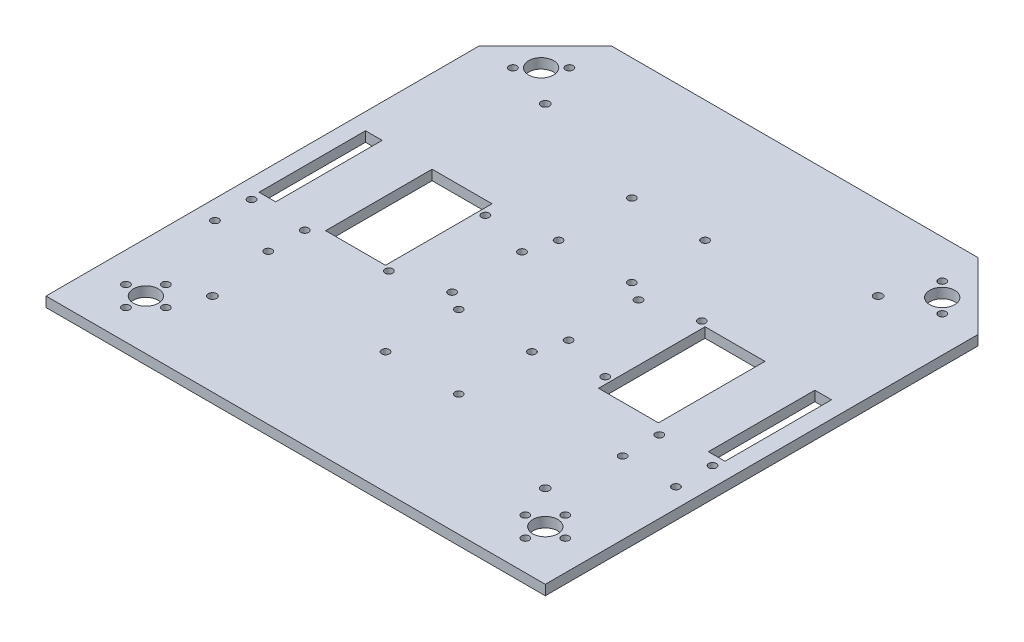
SolidWorks part; units mm, degrees
ref_plane "Plan de face" through (0, 0, 0) normal (0, 0, 1) x (1, 0, 0)
ref_plane "Plan de dessus" through (0, 0, 0) normal (0, 1, 0) x (1, 0, 0)
ref_plane "Plan de droite" through (0, 0, 0) normal (1, 0, 0) x (0, 0, -1)
sketch "Esquisse1" plane through (0, 0, 0) normal (0, 1, 0) x (1, 0, 0)
  line L0 (-150, 0) -> (-150, 260)
  line L2 (150, 0) -> (150, 260)
  line L3 (-150, 260) -> (-110, 260) construction
  line L4 (-110, 260) -> (-110, 300) construction
  line L5 (150, 260) -> (110, 260) construction
  line L6 (110, 260) -> (110, 300) construction
  line L8 (-150, 260) -> (-110, 300)
  line L9 (-110, 300) -> (110, 300)
  line L10 (0, 0) -> (0, 300) construction
  line L11 (110, 300) -> (150, 260)
  line L12 (-150, 0) -> (-120, 0) construction
  line L13 (-120, 18) -> (-120, 0) construction
  line L14 (150, 0) -> (120, 0) construction
  line L15 (120, 18) -> (120, 0) construction
  line L17 (-150, 260) -> (-120, 260) construction
  line L18 (-120, 260) -> (-120, 267.5) construction
  line L19 (150, 260) -> (120, 260) construction
  line L20 (120, 260) -> (120, 268.5) construction
  line L21 (-120, 267.5) -> (-111.5147, 275.9853) construction
  line L22 (-120, 267.5) -> (-128.4853, 259.0147) construction
  line L23 (120, 268.5) -> (128.4853, 260.0147) construction
  line L24 (120, 268.5) -> (111.5147, 276.9853) construction
  line L25 (-150, 0) -> (150, 0) construction
  line L26 (120, 30) -> (120, 18) construction
  line L27 (120, 30) -> (120, 42) construction
  line L28 (-150, 0) -> (150, 0)
  line L29 (-120, 18) -> (-120, 30) construction
  line L30 (-120, 30) -> (-120, 42) construction
  line L32 (150, 150) -> (-150, 150) construction
  line L33 (-120, 30) -> (-108, 30) construction
  line L34 (-120, 30) -> (-132, 30) construction
  line L35 (120, 30) -> (132, 30) construction
  line L36 (120, 30) -> (108, 30) construction
  circle A2 centre (-120, 30) radius 7.5
  circle A4 centre (-120, 267.5) radius 7.5
  circle A5 centre (120, 268.5) radius 7.5
  circle A6 centre (-111.5147, 275.9853) radius 2.3
  circle A7 centre (-128.4853, 259.0147) radius 2.3
  circle A8 centre (111.5147, 276.9853) radius 2.3
  circle A9 centre (128.4853, 260.0147) radius 2.3
  circle A10 centre (120, 30) radius 7.5
  circle A11 centre (120, 42) radius 2.3
  circle A13 centre (-120, 42) radius 2.3
  circle A14 centre (-120, 18) radius 2.3
  circle A16 centre (-132, 30) radius 2.3
  circle A17 centre (-108, 30) radius 2.3
  circle A18 centre (108, 30) radius 2.3
  circle A19 centre (132, 30) radius 2.3
  circle A20 centre (120, 18) radius 2.3
extrude "Boss.-Extru.1" add sketch "Esquisse1" along normal blind 6
sketch "Esquisse7" plane through (0, 6, 0) normal (0, 1, 0) x (1, 0, 0)
  line L0 (0, 150) -> (-130, 150) construction
  line L1 (0, 0) -> (0, 300) construction
  line L2 (150, 150) -> (-150, 150) construction
  line L3 (-130, 150) -> (-130, 182)
  line L4 (-130, 182) -> (-140, 182)
  line L5 (-140, 182) -> (-140, 118)
  line L6 (-140, 118) -> (-130, 118)
  line L7 (-130, 118) -> (-130, 150)
extrude "Enlèv. mat.-Extru.9" cut sketch "Esquisse7" against normal blind 10.5
sketch "Esquisse6" plane through (0, 6, 0) normal (0, 1, 0) x (1, 0, 0)
  line L0 (-142.5, 116) -> (-134.5, 116) construction
  line L2 (-142.5, 116) -> (-142.5, 150) construction
  line L3 (-142.5, 116) -> (-142.5, 108) construction
  line L11 (-142.5, 108) -> (-134.5, 108) construction
  line L12 (-134.5, 108) -> (-134.5, 116) construction
  line L14 (-142.5, 150) -> (-150, 150) construction
  line L15 (-142.5, 116) -> (-102.5, 116) construction
  line L16 (-102.5, 116) -> (-102.5, 108) construction
  line L17 (-102.5, 108) -> (-110.5, 108) construction
  line L18 (-110.5, 108) -> (-110.5, 116) construction
  line L19 (-110.5, 116) -> (-134.5, 116) construction
  line L20 (-134.5, 116) -> (-134.5, 86) construction
  line L21 (-134.5, 86) -> (-142.5, 86) construction
  line L22 (-142.5, 86) -> (-142.5, 94) construction
  line L23 (-142.5, 94) -> (-134.5, 94) construction
  line L24 (-134.5, 94) -> (-134.5, 86) construction
  line L25 (-134.5, 86) -> (-110.5, 86) construction
  line L26 (-110.5, 86) -> (-110.5, 94) construction
  line L27 (-110.5, 94) -> (-102.5, 94) construction
  line L28 (-102.5, 94) -> (-102.5, 86) construction
  line L29 (-102.5, 86) -> (-110.5, 86) construction
  line L30 (-102.5, 94) -> (-110.5, 86) construction
  line L31 (-110.5, 94) -> (-102.5, 86) construction
  line L32 (-142.5, 94) -> (-134.5, 86) construction
  line L33 (-142.5, 86) -> (-134.5, 94) construction
  line L34 (-142.5, 116) -> (-134.5, 108) construction
  line L35 (-142.5, 108) -> (-134.5, 116) construction
  line L71 (-110.5, 116) -> (-102.5, 108) construction
  line L72 (-110.5, 108) -> (-102.5, 116) construction
  line L73 (-110.5, 116) -> (-110.5, 86) construction
  circle A20 centre (-138.5, 90) radius 2.3
  circle A21 centre (-138.5, 112) radius 2.3
  circle A22 centre (-106.5, 112) radius 2.3
  circle A23 centre (-106.5, 90) radius 2.3
  dimension "D1" = 7.5
  dimension "D2" = 34
sketch "Esquisse4" plane through (0, 6, 0) normal (0, 1, 0) x (1, 0, 0)
  line L0 (-150, 150) -> (-100, 150) construction
  line L8 (150, 150) -> (-150, 150) construction
  line L14 (-100, 150) -> (-100, 182)
  line L15 (-100, 250) -> (-100, 50) construction
  line L16 (-100, 150) -> (-100, 118)
  line L17 (-100, 118) -> (-64, 118)
  line L18 (-64, 118) -> (-64, 182)
  line L19 (-64, 182) -> (-100, 182)
sketch "Esquisse9" plane through (0, 6, 0) normal (0, 1, 0) x (1, 0, 0)
  line L0 (-150, 0) -> (150, 0) construction
  line L1 (150, 0) -> (150, 300) construction
  line L2 (150, 300) -> (-150, 300) construction
  line L3 (-150, 300) -> (-150, 0) construction
  line L5 (-150, 0) -> (-150, 300) construction
  line L6 (150, 0) -> (0, 0) construction
  line L7 (0, 0) -> (0, 50) construction
  line L8 (0, 0) -> (0, 300) construction
  line L9 (0, 50) -> (100, 50) construction
  line L10 (100, 50) -> (100, 250) construction
  line L11 (100, 250) -> (-100, 250) construction
  line L12 (-100, 250) -> (-100, 50) construction
  line L13 (-100, 50) -> (0, 50) construction
  line L18 (100, 250) -> (94.3431, 244.3431) construction
  line L21 (-150, 0) -> (150, 300) construction
  circle A0 centre (-100, 50) radius 2.5
  circle A1 centre (100, 50) radius 2.5
  circle A2 centre (100, 250) radius 2.5
  circle A3 centre (-100, 250) radius 2.5
extrude "Enlèv. mat.-Extru.10" cut sketch "Esquisse6" against normal blind 50
extrude "Enlèv. mat.-Extru.11" cut sketch "Esquisse4" against normal blind 50
sketch "Esquisse3" plane through (0, 6, 0) normal (0, 1, 0) x (1, 0, 0)
  line L6 (-150, 150) -> (-64, 150) construction
  line L7 (-64, 118) -> (-64, 182) construction
  line L8 (-64, 150) -> (-64, 178) construction
  line L9 (-64, 178) -> (-56, 178) construction
  line L10 (-56, 178) -> (-56, 170) construction
  line L11 (-56, 170) -> (-59, 170) construction
  line L16 (-64, 150) -> (-64, 112) construction
  line L17 (-64, 112) -> (-56, 112) construction
  line L25 (-56, 112) -> (-56, 120) construction
  line L26 (-64, 120) -> (-34, 120) construction
  line L27 (-56, 170) -> (-64, 178) construction
  line L28 (-64, 178) -> (-56, 178) construction
  line L29 (-56, 178) -> (-64, 170) construction
  line L30 (-34, 120) -> (-26, 120) construction
  line L31 (-56, 112) -> (-64, 120) construction
  line L32 (-64, 120) -> (-56, 120) construction
  line L33 (-56, 120) -> (-64, 112) construction
  line L37 (-26, 120) -> (-26, 128) construction
  line L38 (-26, 128) -> (-34, 128) construction
  line L39 (-34, 128) -> (-26, 120) construction
  line L43 (-26, 120) -> (-34, 120) construction
  line L55 (150, 150) -> (64, 150) construction
  line L56 (150, 150) -> (-150, 150) construction
  line L57 (64, 150) -> (64, 170) construction
  line L58 (34, 130) -> (26, 130) construction
  line L61 (64, 150) -> (64, 130) construction
  line L62 (64, 130) -> (59, 130) construction
  line L63 (59, 130) -> (59, 165) construction
  line L66 (59, 165) -> (39, 165) construction
  line L70 (39, 165) -> (39, 130) construction
  line L72 (39, 130) -> (34, 130) construction
  line L73 (34, 130) -> (34, 180) construction
  line L74 (34, 180) -> (64, 180) construction
  line L76 (64, 180) -> (64, 130) construction
  line L77 (-34, 120) -> (-26, 128) construction
  line L78 (26, 130) -> (26, 138) construction
  line L79 (-34, 120) -> (-34, 170) construction
  line L80 (-39, 170) -> (-34, 170) construction
  line L81 (-34, 170) -> (-26, 170) construction
  line L82 (-26, 170) -> (-26, 162) construction
  line L83 (-26, 162) -> (-34, 162) construction
  line L84 (-34, 162) -> (-26, 170) construction
  line L85 (-26, 170) -> (-34, 170) construction
  line L86 (-34, 170) -> (-26, 162) construction
  line L87 (26, 138) -> (34, 138) construction
  line L88 (-59, 170) -> (-59, 138) construction
  line L89 (-59, 138) -> (-39, 138) construction
  line L90 (-39, 138) -> (-39, 170) construction
  line L91 (34, 138) -> (26, 130) construction
  line L92 (26, 130) -> (26, 138) construction
  line L93 (26, 138) -> (34, 130) construction
  line L94 (34, 130) -> (34, 180) construction
  line L95 (34, 180) -> (26, 180) construction
  line L96 (26, 180) -> (26, 172) construction
  line L97 (26, 172) -> (34, 172) construction
  line L98 (34, 172) -> (26, 180) construction
  line L99 (26, 180) -> (26, 172) construction
  line L100 (26, 172) -> (34, 180) construction
  line L101 (64, 180) -> (64, 188) construction
  line L102 (64, 188) -> (56, 188) construction
  line L103 (56, 188) -> (56, 180) construction
  line L104 (56, 180) -> (64, 188) construction
  line L105 (64, 188) -> (56, 188) construction
  line L106 (56, 188) -> (64, 180) construction
  line L107 (64, 180) -> (64, 130) construction
  line L108 (64, 130) -> (64, 122) construction
  line L109 (64, 122) -> (56, 122) construction
  line L110 (56, 122) -> (56, 130) construction
  line L111 (56, 130) -> (59, 130) construction
  line L112 (64, 122) -> (56, 130) construction
  line L113 (56, 130) -> (56, 122) construction
  line L114 (56, 122) -> (64, 130) construction
  circle A8 centre (-60, 174) radius 2.3
  circle A10 centre (-60, 116) radius 2.3
  circle A12 centre (-30, 166) radius 2.3
  circle A13 centre (-30, 124) radius 2.3
  circle A14 centre (60, 184) radius 2.3
  circle A15 centre (30, 176) radius 2.3
  circle A16 centre (30, 134) radius 2.3
  circle A17 centre (60, 126) radius 2.3
mirror "Symétrie1" about plane through (0, 0, 0) normal (1, 0, 0) of "Enlèv. mat.-Extru.9"
mirror "Symétrie2" about plane through (0, 0, 0) normal (1, 0, 0) of "Enlèv. mat.-Extru.11"
mirror "Symétrie3" about plane through (0, 0, 0) normal (1, 0, 0) of "Enlèv. mat.-Extru.10"
extrude "Enlèv. mat.-Extru.12" cut sketch "Esquisse9" against normal blind 35
extrude "Enlèv. mat.-Extru.13" cut sketch "Esquisse3" against normal blind 35
sketch "Esquisse10" plane through (0, 6, 0) normal (0, 1, 0) x (1, 0, 0)
  line L0 (0, 150) -> (0, 205) construction
  line L1 (-37, 187) -> (-51.6, 187) construction
  line L2 (-37, 187) -> (-37, 223) construction
  line L3 (0, 113) -> (37, 113) construction
  line L4 (37, 113) -> (37, 77) construction
  line L5 (37, 77) -> (-23, 77) construction
  line L6 (-23, 77) -> (-23, 113) construction
  line L7 (-23, 113) -> (37, 113) construction
  line L8 (-37, 187) -> (23, 187) construction
  line L9 (-28.9998, 231) -> (-20.9998, 231) construction
  line L10 (29, 69) -> (29, 77) construction
  line L11 (-20.9998, 231) -> (-20.9998, 223) construction
  line L12 (-20.9998, 223) -> (-28.9998, 231) construction
  line L13 (-28.9998, 231) -> (-20.9998, 231) construction
  line L14 (-20.9998, 231) -> (-28.9998, 223) construction
  line L15 (-37, 187) -> (-28.9998, 187) construction
  line L16 (29, 121) -> (29, 113) construction
  line L17 (37, 95) -> (56.6, 95) construction
  line L18 (29, 69) -> (29, 77) construction
  line L19 (29, 113) -> (-23, 113) construction
  line L20 (29, 77) -> (-23, 77) construction
  line L21 (-23, 77) -> (-23, 69) construction
  line L22 (-23, 69) -> (-15, 69) construction
  line L23 (-15, 69) -> (-15, 77) construction
  line L24 (-28.9998, 187) -> (-20.9998, 187) construction
  line L25 (29, 121) -> (21, 121) construction
  line L26 (-15, 77) -> (-23, 69) construction
  line L27 (-23, 69) -> (-23, 77) construction
  line L28 (-23, 77) -> (-15, 69) construction
  line L29 (-20.9998, 187) -> (-20.9998, 179) construction
  line L30 (-20.9998, 179) -> (-28.9998, 179) construction
  line L31 (-28.9998, 179) -> (-28.9998, 187) construction
  line L32 (-23, 113) -> (-23, 121) construction
  line L33 (-23, 121) -> (-15, 121) construction
  line L34 (-15, 121) -> (-15, 113) construction
  line L35 (-28.9998, 187) -> (-20.9998, 179) construction
  line L36 (-20.9998, 179) -> (-20.9998, 187) construction
  line L37 (23, 187) -> (23, 223) construction
  line L38 (23, 223) -> (-37, 223) construction
  line L39 (-37, 223) -> (23, 223) construction
  line L40 (23, 223) -> (23, 231) construction
  line L41 (23, 231) -> (15, 231) construction
  line L42 (0, 95) -> (37, 95) construction
  line L43 (-20.9998, 187) -> (-28.9998, 179) construction
  line L44 (15, 231) -> (23, 223) construction
  line L45 (23, 223) -> (23, 231) construction
  line L46 (-23, 121) -> (-15, 113) construction
  line L47 (0, 205) -> (-37, 205) construction
  line L48 (-15, 113) -> (-15, 121) construction
  line L49 (-15, 121) -> (-23, 113) construction
  line L50 (23, 231) -> (15, 223) construction
  line L51 (15, 223) -> (15, 231) construction
  line L52 (15, 231) -> (23, 223) construction
  line L53 (23, 223) -> (23, 187) construction
  line L54 (23, 187) -> (23, 179) construction
  line L55 (23, 179) -> (15, 179) construction
  line L56 (15, 179) -> (15, 187) construction
  line L57 (15, 187) -> (23, 179) construction
  line L58 (23, 179) -> (23, 187) construction
  line L59 (23, 187) -> (15, 179) construction
  line L64 (29, 121) -> (37, 121)
  line L71 (-28.9998, 231) -> (-28.9998, 223) construction
  line L73 (-52, 205) -> (-37, 205) construction
  line L74 (21, 121) -> (21, 113) construction
  line L75 (21, 113) -> (29, 121) construction
  line L76 (29, 121) -> (21, 121) construction
  line L77 (21, 121) -> (29, 113) construction
  line L78 (0, 0) -> (0, 300) construction
  line L79 (0, 150) -> (0, 95) construction
  line L80 (-37, 223) -> (-37, 231) construction
  line L81 (29, 69) -> (21, 69) construction
  line L82 (21, 69) -> (21, 77) construction
  line L84 (-28.9998, 223) -> (-37, 231) construction
  line L86 (21, 77) -> (29, 69) construction
  line L87 (29, 69) -> (29, 77) construction
  line L88 (29, 77) -> (21, 69) construction
  line L89 (-28.9998, 223) -> (-28.9998, 231) construction
  line L90 (-28.9998, 231) -> (-37, 223) construction
  circle A22 centre (-19, 73) radius 2.3
  circle A30 centre (-19, 117) radius 2.3
  circle A35 centre (25, 73) radius 2.3
  circle A36 centre (25, 117) radius 2.3
  circle A37 centre (-24.9998, 227) radius 2.3
  circle A39 centre (-24.9998, 183) radius 2.3
  circle A40 centre (19, 183) radius 2.3
  circle A41 centre (19, 227) radius 2.3
extrude "Enlèv. mat.-Extru.14" cut sketch "Esquisse10" against normal blind 10 contours A35 | A22 | A30 | A40 | A41 | A37 | A39 | A36 region at (-19, 6, -73) region at (-19, 6, -117) region at (25, 6, -73) region at (19, 6, -183) region at (19, 6, -227)
